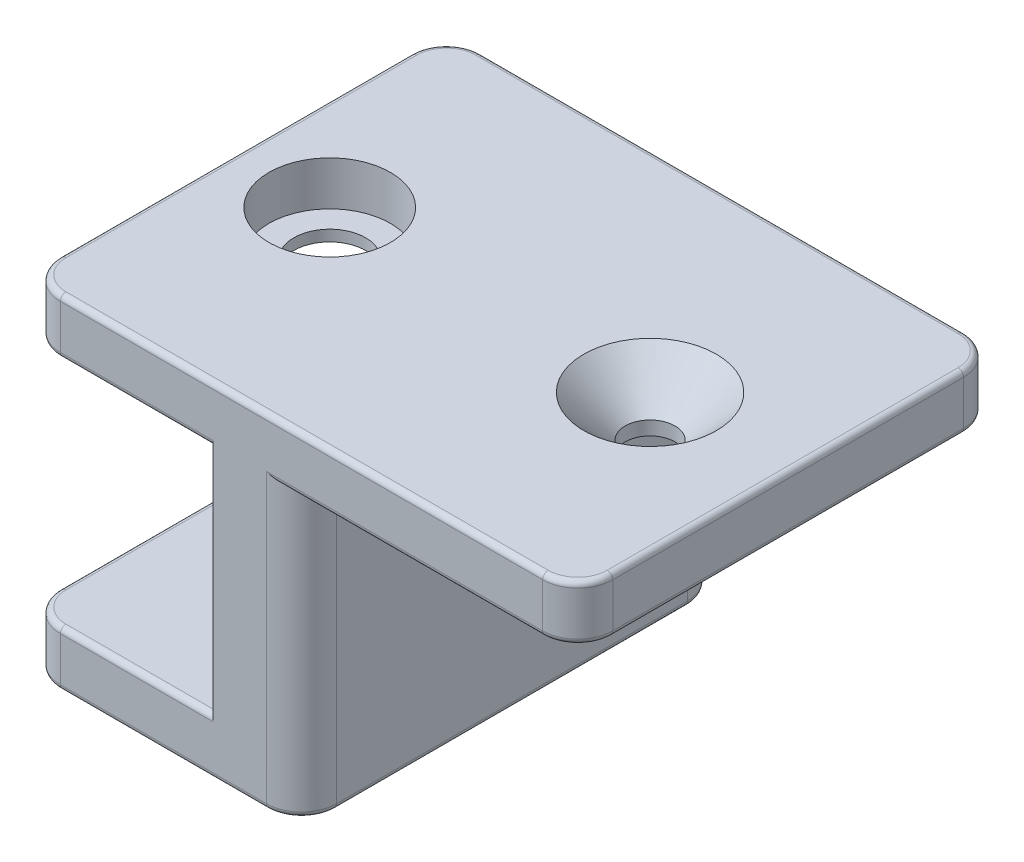
SolidWorks part; units mm, degrees
material "ABS"
ref_plane "Front Plane" through (0, 0, 0) normal (0, 0, 1) x (1, 0, 0)
ref_plane "Top Plane" through (0, 0, 0) normal (0, 1, 0) x (1, 0, 0)
ref_plane "Right Plane" through (0, 0, 0) normal (1, 0, 0) x (0, 0, -1)
sketch "Sketch1" plane through (0, 0, 0) normal (0, 1, 0) x (1, 0, 0)
  line L1 (-12.5, 34.05) -> (12.5, 34.05)
  line L2 (-12.5, 34.05) -> (-12.5, -34.05)
  line L3 (-12.5, -34.05) -> (12.5, -34.05)
  line L4 (12.5, 34.05) -> (12.5, -34.05)
  line L5 (-12.5, 34.05) -> (12.5, -34.05) construction
  line L6 (-12.5, -34.05) -> (12.5, 34.05) construction
  point P0 (0, 0)
  dimension "D1" = 68.1
  dimension "D2" = 25
extrude "Boss-Extrude1" add sketch "Sketch1" against normal blind 31.05
sketch "Sketch2" plane through (12.5, 0, 0) normal (1, 0, 0) x (0, 0, -1)
  line L0 (0, 0) -> (0, -31.05) construction
  line L1 (-34.05, 0) -> (34.05, 0) construction
  line L2 (-34.05, -31.05) -> (34.05, -31.05) construction
  line L3 (-34.05, -5) -> (-19.05, -5)
  line L4 (-34.05, -31.05) -> (-34.05, 0) construction
  line L5 (-19.05, -5) -> (-19.05, -31.05)
  line L6 (-19.05, -31.05) -> (-34.05, -31.05)
  line L7 (-34.05, -31.05) -> (-34.05, -5)
  line L8 (34.05, -5) -> (19.05, -5)
  line L9 (34.05, -31.05) -> (34.05, 0) construction
  line L10 (19.05, -5) -> (19.05, -31.05)
  line L11 (19.05, -31.05) -> (34.05, -31.05)
  line L12 (34.05, -31.05) -> (34.05, -5)
  dimension "D1" = 5
  dimension "D2" = 19.05
extrude "Cut-Extrude1" cut sketch "Sketch2" against normal up to next
sketch "Sketch3" plane through (0, 0, 0) normal (0, 0, 1) x (1, 0, 0)
  line L0 (-12.5, -5) -> (4.5, -5)
  line L1 (4.5, -5) -> (4.5, -26.05)
  line L2 (4.5, -26.05) -> (-12.5, -26.05)
  line L3 (-12.5, -26.05) -> (-12.5, -5)
  line L4 (-12.5, -31.05) -> (-12.5, -5) construction
  line L7 (-12.5, -5) -> (12.5, -5) construction
  line L10 (-12.5, -31.05) -> (12.5, -31.05) construction
  dimension "D1" = 17
  dimension "D2" = 5
  dimension "D3" = 21.05
extrude "Cut-Extrude2" cut sketch "Sketch3" along normal mid plane 50
sketch "Sketch4" plane through (0, 0, 0) normal (0, 1, 0) x (1, 0, 0)
  line L0 (-12.5, 0) -> (4.5, 0) construction
  line L1 (-12.5, 34.05) -> (-12.5, -34.05) construction
  line L2 (4.5, -19.05) -> (4.5, 19.05) construction
  line L3 (0, -19.05) -> (0, -34.05) construction
  line L4 (-12.5, -34.05) -> (12.5, -34.05) construction
  line L5 (4.5, -19.05) -> (12.5, -19.05) construction
  point P8 (-4, 0)
  point P15 (0, -26.55)
sketch "Sketch6" plane through (0, 0, 0) normal (0, 0, 1) x (1, 0, 0)
  line L0 (-4, 0) -> (-4, -5)
  line L1 (-12.5, 0) -> (4.5, 0) construction
  line L2 (-4, -5) -> (-0.75, -5)
  line L3 (-0.75, -5) -> (-0.75, -4)
  line L4 (-0.75, -4) -> (1.5, -4)
  line L5 (1.5, -4) -> (1.5, 0)
  line L6 (1.5, 0) -> (-4, 0)
  line L7 (-12.5, -5) -> (12.5, -5) construction
  dimension "D1" = 4
  dimension "D2" = 3.25
  dimension "D3" = 5.5
revolve "Cut-Revolve2" cut sketch "Sketch6" angle 360 about L0
sketch "Sketch7" plane through (0, 0, 0) normal (0, 1, 0) x (1, 0, 0)
  line L0 (0, 0) -> (37.5, 0) construction
  line L1 (12.5, 19.05) -> (12.5, -19.05)
  line L2 (12.5, -34.05) -> (12.5, 34.05) construction
  line L3 (12.5, -19.05) -> (37.5, -19.05)
  line L4 (37.5, -19.05) -> (37.5, 19.05)
  line L5 (37.5, 19.05) -> (12.5, 19.05)
  line L6 (4.5, 19.05) -> (-12.5, 19.05) construction
  line L7 (-12.5, -19.05) -> (4.5, -19.05) construction
  dimension "D1" = 25
extrude "Boss-Extrude2" add sketch "Sketch7" against normal up to surface (5 mm away) up to face at (-7.25, -5, 0)
sketch "Sketch10" plane through (0, 0, 0) normal (0, 0, 1) x (1, 0, 0)
  line L0 (12.5, 0) -> (37.5, 0) construction
  line L1 (1.5, 0) -> (-9.5, 0) construction
  line L2 (25, 0) -> (19, 0)
  line L3 (19, 0) -> (22.75, -3.75)
  line L4 (22.75, -3.75) -> (22.75, -5)
  line L5 (22.75, -5) -> (25, -5)
  line L6 (25, -5) -> (25, 0)
  line L7 (37.5, -5) -> (12.5, -5) construction
  point P5 (25, 0)
  dimension "D1" = 25
  dimension "D2" = 2.25
  dimension "D3" = 6
  dimension "D4" = 45
revolve "Cut-Revolve3" cut sketch "Sketch10" angle 360 about L6
sketch "Sketch11" plane through (0, 0, 0) normal (0, 1, 0) x (1, 0, 0)
  line L0 (12.5, 19.05) -> (-12.5, 19.05)
  line L1 (-12.5, 34.05) -> (-12.5, -34.05) construction
  line L2 (-12.5, 19.05) -> (-12.5, 34.05)
  line L3 (-12.5, 34.05) -> (12.5, 34.05)
  line L4 (12.5, 34.05) -> (12.5, 19.05)
  line L5 (12.5, -19.05) -> (-12.5, -19.05)
  line L6 (-12.5, -19.05) -> (-12.5, -34.05)
  line L7 (-12.5, -34.05) -> (12.5, -34.05)
  line L8 (12.5, -34.05) -> (12.5, -19.05)
extrude "Cut-Extrude3" cut sketch "Sketch11" against normal up to surface (5 mm away) up to face at (-7.25, -5, 0)
fillet "Fillet1" radius 3.175 2 edges at (12.5, -18.025, 19.05) (12.5, -18.025, -19.05)
fillet "Fillet2" radius 0.5 19 edges at (-1.5875, -31.05, 19.05) (11.5701, -31.05, 18.1201) (12.5, -31.05, 0) (11.5701, -31.05, -18.1201) (-4, -26.05, 19.05) (-12.5, -26.05, 0) (-4, -26.05, -19.05) (-12.5, -31.05, 0) (-1.5875, -31.05, -19.05) (37.5, 0, 0) (12.5, 0, 19.05) (-12.5, 0, 0) (12.5, 0, -19.05) (-4, -5, -19.05) (-12.5, -5, 0) (-4, -5, 19.05) (23.4125, -5, 19.05) (37.5, -5, 0) (23.4125, -5, -19.05)
fillet "Fillet3" radius 3.175 18 edges at (37.3536, -0.1464, -18.9036) (37.3536, -4.8536, -18.9036) (37.3536, -0.1464, 18.9036) (37.3536, -4.8536, 18.9036) (-12.3536, -0.1464, 18.9036) (-12.3536, -4.8536, 18.9036) (-12.3536, -0.1464, -18.9036) (-12.3536, -4.8536, -18.9036) (-12.5, -2.5, -19.05) (-12.5, -2.5, 19.05) (37.5, -2.5, 19.05) (37.5, -2.5, -19.05) (-12.3536, -30.9036, -18.9036) (-12.3536, -26.1964, -18.9036) (-12.3536, -26.1964, 18.9036) (-12.3536, -30.9036, 18.9036) (-12.5, -28.55, 19.05) (-12.5, -28.55, -19.05)
